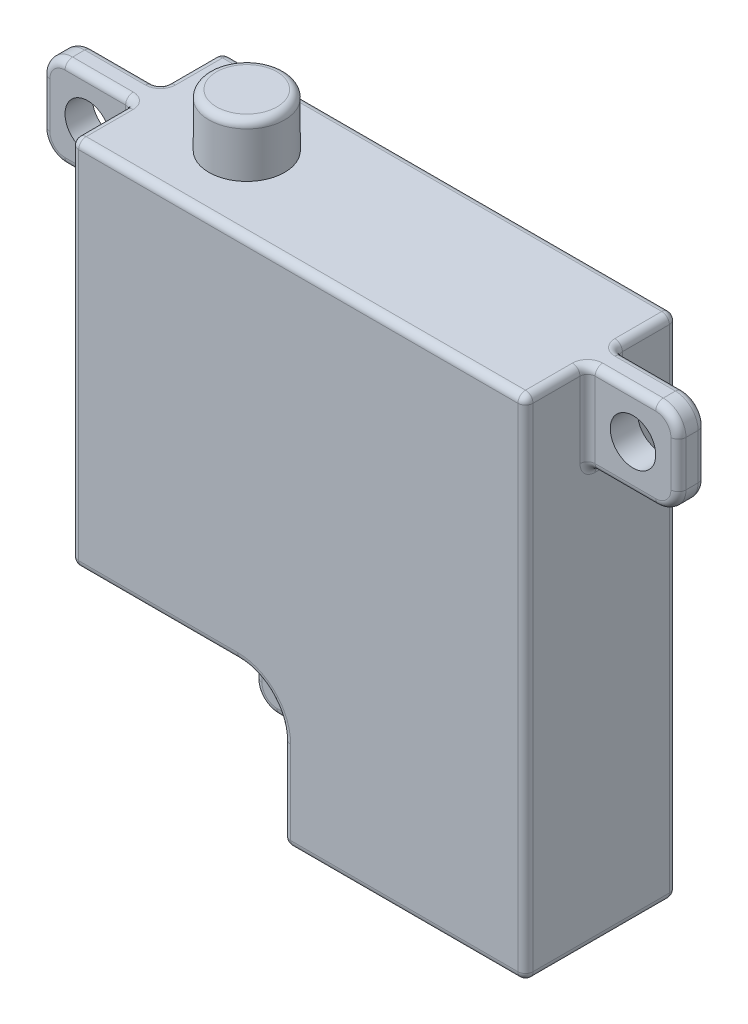
SolidWorks part; units mm, degrees
ref_plane "Front Plane" through (0, 0, 0) normal (0, 0, 1) x (1, 0, 0)
ref_plane "Top Plane" through (0, 0, 0) normal (0, 1, 0) x (1, 0, 0)
ref_plane "Right Plane" through (0, 0, 0) normal (1, 0, 0) x (0, 0, -1)
sketch "Sketch1" plane through (0, 0, 0) normal (0, 0, 1) x (1, 0, 0)
  line L0 (0, 0) -> (16, 0)
  line L1 (16, 0) -> (16, 33.5)
  line L2 (16, 33.5) -> (-14, 33.5)
  line L3 (-14, 33.5) -> (-14, 9)
  line L4 (-14, 9) -> (-3, 9)
  line L5 (0, 0) -> (0, 6)
  arc A0 (-3, 9) -> (0, 6) centre (-3, 6) cw
  dimension "D3" = 3
  dimension "D1" = 30
  dimension "D2" = 33.5
  dimension "D4" = 9
  dimension "D5" = 11
extrude "Boss-Extrude1" add sketch "Sketch1" along normal blind 10
sketch "Sketch2" plane through (-14, 0, 0) normal (-1, 0, 0) x (0, 0, 1)
  line L0 (5, 33.5) -> (5, 9) construction
  line L1 (10, 33.5) -> (0, 33.5) construction
  line L2 (10, 9) -> (0, 9) construction
  line L4 (4.1, 33.5) -> (5.9, 33.5)
  line L5 (4.1, 33.5) -> (4.1, 27.5)
  line L6 (4.1, 27.5) -> (5.9, 27.5)
  line L7 (5.9, 33.5) -> (5.9, 27.5)
  point P11 (5, 33.5)
  dimension "D1" = 1.8
  dimension "D2" = 6
extrude "Boss-Extrude2" add sketch "Sketch2" along normal blind 6
sketch "Sketch3" plane through (16, 0, 0) normal (1, 0, 0) x (0, 0, -1)
  line L0 (-5, 33.5) -> (-5, 0) construction
  line L1 (-10, 33.5) -> (0, 33.5) construction
  line L2 (-10, 0) -> (0, 0) construction
  line L4 (-5.9, 33.5) -> (-4.1, 33.5)
  line L5 (-5.9, 33.5) -> (-5.9, 27.5)
  line L6 (-5.9, 27.5) -> (-4.1, 27.5)
  line L7 (-4.1, 33.5) -> (-4.1, 27.5)
  point P10 (-5, 33.5)
  dimension "D1" = 1.8
  dimension "D2" = 6
extrude "Boss-Extrude3" add sketch "Sketch3" along normal blind 6
sketch "Sketch4" plane through (0, 0, 0) normal (-1, 0, 0) x (0, 0, 1)
  line L0 (5, 0) -> (5, 9) construction
  line L1 (10, 0) -> (0, 0) construction
  line L2 (10, 9) -> (0, 9) construction
  line L4 (4.1, 9) -> (5.9, 9)
  line L5 (4.1, 9) -> (4.1, 3)
  line L6 (4.1, 3) -> (5.9, 3)
  line L7 (5.9, 9) -> (5.9, 3)
  point P10 (5, 9)
  dimension "D1" = 1.8
  dimension "D2" = 6
extrude "Boss-Extrude4" add sketch "Sketch4" along normal blind 6
sketch "Sketch5" plane through (0, 0, 5.9) normal (0, 0, 1) x (1, 0, 0)
  line L0 (-20, 33.5) -> (-14, 33.5) construction
  line L1 (-20, 27.5) -> (-20, 33.5) construction
  line L2 (22, 33.5) -> (16, 33.5) construction
  line L3 (-20, 27.5) -> (-14, 27.5) construction
  line L5 (-6, 3) -> (-6, 9) construction
  line L6 (-6, 3) -> (0, 3) construction
  line L7 (22, 33.5) -> (22, 27.5) construction
  line L8 (22, 27.5) -> (16, 27.5) construction
  line L9 (20.5, 33.5) -> (22, 33.5)
  line L10 (22, 33.5) -> (22, 32)
  line L13 (20.5, 27.5) -> (22, 27.5)
  line L14 (22, 27.5) -> (22, 29)
  line L15 (-6, 4.5) -> (-6, 3)
  line L16 (-6, 3) -> (-4.5, 3)
  circle A0 centre (-17, 30.5) radius 1.5
  circle A1 centre (19, 30.5) radius 1.5
  circle A2 centre (-3, 6) radius 1.5
  arc A3 (-20, 32) -> (-18.5, 33.5) centre (-18.5, 32) cw
  arc A4 (-20, 29) -> (-18.5, 27.5) centre (-18.5, 29) ccw
  arc A5 (-6, 4.5) -> (-4.5, 3) centre (-4.5, 4.5) ccw
  arc A6 (20.5, 33.5) -> (22, 32) centre (20.5, 32) cw
  arc A7 (20.5, 27.5) -> (22, 29) centre (20.5, 29) ccw
  point P10 (-17, 33.5)
  point P14 (-20, 30.5)
  point P17 (19, 33.5)
  line M5 (-14, 33.5) -> (-20, 33.5)
  line M6 (-20, 33.5) -> (-20, 27.5)
  line M7 (-20, 27.5) -> (-14, 27.5)
  dimension "D1" = 3
  dimension "D2" = 1.5
  dimension "D4" = 24.5
  dimension "D5" = 14
extrude "Cut-Extrude2" cut sketch "Sketch5" against normal blind 6 contours A5 L15 L16 | A2 | A4 M6 M7 | A3 M6 M5 | A0 | A1 | L9 A6 L10 | A7 L13 L14 region at (21.6649, 33.1649, 5.9) region at (21.6649, 27.8351, 5.9) region at (-5.6649, 3.3351, 5.9) region at (-17, 30.5, 5.9) region at (19, 30.5, 5.9) region at (-3, 6, 5.9) region at (-19.6649, 33.1649, 5.9) region at (-19.6649, 27.8351, 5.9)
fillet "Fillet1" radius 0.5 63 edges at (-6, 9, 5) (0, 3, 5) (-16.25, 27.5, 5.9) (-19.5607, 27.9393, 5.9) (-20, 30.5, 5.9) (-19.5607, 33.0607, 5.9) (-16.25, 27.5, 4.1) (-19.5607, 27.9393, 4.1) (-20, 30.5, 4.1) (-19.5607, 33.0607, 4.1) (18.25, 27.5, 4.1) (21.5607, 27.9393, 4.1) (22, 30.5, 4.1) (21.5607, 33.0607, 4.1) (18.25, 27.5, 5.9) (21.5607, 27.9393, 5.9) (22, 30.5, 5.9) (21.5607, 33.0607, 5.9) (16, 27.5, 5) (16, 30.5, 4.1) (16, 30.5, 5.9) (-0.8787, 8.1213, 10) (-8.5, 9, 10) (16, 16.75, 10) (0, 3, 10) (-2.25, 3, 4.1) (0, 4.5, 4.1) (-0.8787, 8.1213, 4.1) (-4.5, 9, 4.1) (-6, 6.75, 4.1) (-5.5607, 3.4393, 4.1) (-3, 4.5, 4.1) (-6, 6.75, 5.9) (-4.5, 9, 5.9) (-0.8787, 8.1213, 5.9) (0, 4.5, 5.9) (-2.25, 3, 5.9) (-5.5607, 3.4393, 5.9) (-1.5, 6, 5.9) (-14, 27.5, 5) (-14, 30.5, 5.9) (-14, 21.25, 10) (-14, 9, 5) (-14, 30.5, 4.1) (0, 0, 5) (8, 0, 10) (16, 0, 5) (16, 33.5, 7.95) (1, 33.5, 10) (-14, 33.5, 7.95) (-16.25, 33.5, 5.9) (-16.25, 33.5, 4.1) (-14, 33.5, 2.05) (16, 33.5, 2.05) (18.25, 33.5, 4.1) (18.25, 33.5, 5.9) (8, 0, 0) (16, 16.75, 0) (1, 33.5, 0) (-14, 21.25, 0) (-8.5, 9, 0) (-0.8787, 8.1213, 0) (0, 3, 0)
sketch "Sketch6" plane through (0, 33.5, 0) normal (0, 1, 0) x (1, 0, 0)
  line L0 (-18.5, -5) -> (20.5, -5) construction
  line L1 (-18.5, -4.6) -> (-18.5, -5.4) construction
  line L2 (20.5, -4.6) -> (20.5, -5.4) construction
  line L3 (-14, -3.6) -> (-14, -0.5) construction
  circle A0 centre (-7.4, -5) radius 2.5
  dimension "D1" = 5
  dimension "D2" = 6.6
extrude "Boss-Extrude5" add sketch "Sketch6" along normal blind 3.5
fillet "Fillet2" radius 0.5 1 edges at (-9.9, 37, 5)
